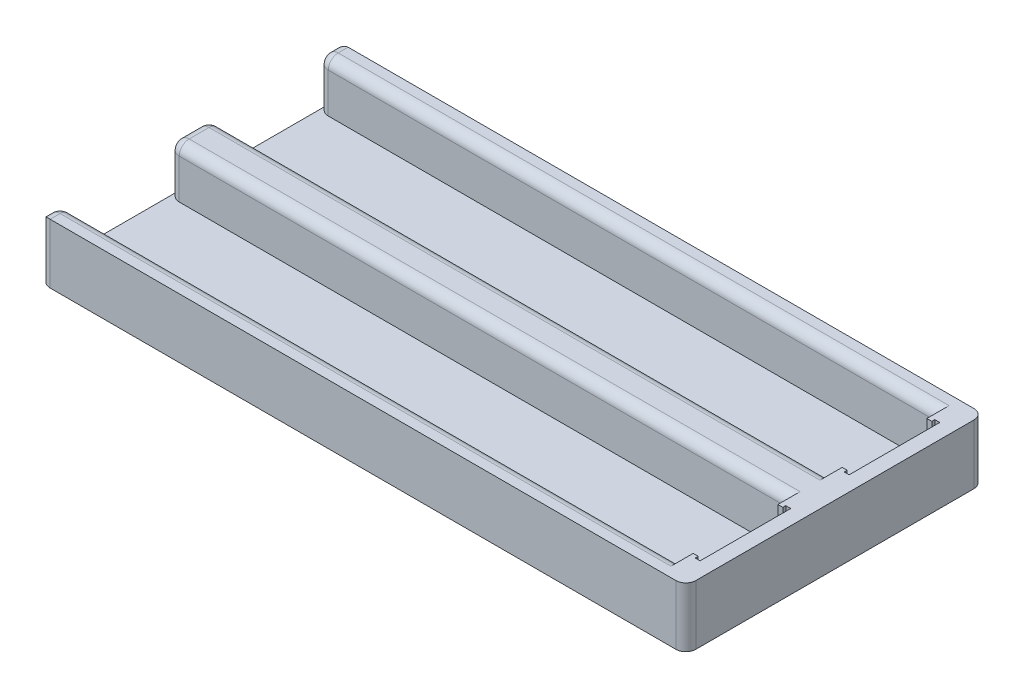
SolidWorks part; units mm, degrees
ref_plane "Front Plane" through (0, 0, 0) normal (0, 0, 1) x (1, 0, 0)
ref_plane "Top Plane" through (0, 0, 0) normal (0, 1, 0) x (1, 0, 0)
ref_plane "Right Plane" through (0, 0, 0) normal (1, 0, 0) x (0, 0, -1)
sketch "Sketch1" plane through (0, 0, 0) normal (0, 1, 0) x (1, 0, 0)
  line L1 (-65, 30) -> (65, 30)
  line L2 (-65, 30) -> (-65, -30)
  line L3 (-65, -30) -> (65, -30)
  line L4 (65, 30) -> (65, -30)
  line L5 (-65, 30) -> (65, -30) construction
  line L6 (-65, -30) -> (65, 30) construction
  point P0 (0, 0)
  dimension "D1" = 130
  dimension "D2" = 60
extrude "Boss-Extrude1" add sketch "Sketch1" along normal blind 12
ref_plane "Plane2" through (60, 0, 0) normal (1, 0, 0) x (0, 0, -1)
sketch "Sketch2" plane through (65, 0, 0) normal (1, 0, 0) x (0, 0, -1)
  line L0 (0, 0) -> (0, 12) construction
  line L1 (30, 0) -> (-30, 0)
  line L2 (30, 0) -> (30, 12)
  line L3 (30, 12) -> (-30, 12)
  line L4 (-30, 0) -> (-30, 12)
  line L5 (30, 0) -> (-30, 12) construction
  line L6 (30, 12) -> (-30, 0) construction
  line L8 (4, 12) -> (26, 12)
  line L9 (4, 12) -> (4, 2)
  line L10 (4, 2) -> (26, 2)
  line L11 (26, 12) -> (26, 2)
  line L12 (4, 12) -> (26, 2) construction
  line L13 (4, 2) -> (26, 12) construction
  point P4 (0, 6)
  point P14 (15, 7)
  dimension "D1" = 4
  dimension "D2" = 4
  dimension "D3" = 10
extrude "Cut-Extrude1" cut sketch "Sketch2" against normal through all from surface contours L11 L3 L9 L10 region at (65, 7, -15) starting at plane "Plane2"
ref_plane "Plane1" through (0, 0, 0) normal (0, 0, 1) x (1, 0, 0)
mirror "Mirror1" about plane through (0, 0, 0) normal (0, 0, 1) of "Cut-Extrude1"
sketch "Sketch3" plane through (60, 0, 0) normal (-1, 0, 0) x (0, 0, 1)
  line L0 (26, 12) -> (4, 12) construction
  line L1 (5.875, 12) -> (24.125, 12)
  line L2 (5.875, 12) -> (5.875, 3)
  line L3 (5.875, 3) -> (24.125, 3)
  line L4 (24.125, 12) -> (24.125, 3)
  line L5 (5.875, 12) -> (24.125, 3) construction
  line L6 (5.875, 3) -> (24.125, 12) construction
  line L7 (15, 7) -> (15, 12) construction
  line L8 (24.125, 12) -> (23.525, 12)
  line L9 (24.125, 12) -> (24.125, 3)
  line L10 (24.125, 3) -> (23.525, 3)
  line L11 (23.525, 12) -> (23.525, 3)
  line L12 (24.125, 12) -> (23.525, 3) construction
  line L13 (24.125, 3) -> (23.525, 12) construction
  line L14 (5.875, 12) -> (6.475, 12)
  line L15 (5.875, 12) -> (5.875, 3)
  line L16 (5.875, 3) -> (6.475, 3)
  line L17 (6.475, 12) -> (6.475, 3)
  line L18 (5.875, 12) -> (6.475, 3) construction
  line L19 (5.875, 3) -> (6.475, 12) construction
  line L20 (5.875, 3) -> (24.125, 3)
  line L21 (5.875, 3) -> (5.875, 3.6)
  line L22 (5.875, 3.6) -> (24.125, 3.6)
  line L23 (24.125, 3) -> (24.125, 3.6)
  line L24 (5.875, 3) -> (24.125, 3.6) construction
  line L25 (5.875, 3.6) -> (24.125, 3) construction
  line L26 (26, 2) -> (4, 2)
  line L27 (26, 2) -> (26, 12) construction
  line L28 (26, 12) -> (4, 12)
  line L29 (4, 2) -> (4, 12) construction
  line L30 (26, 2) -> (4, 12) construction
  line L31 (26, 12) -> (4, 2) construction
  point P4 (15, 7.5)
  point P9 (23.825, 7.5)
  point P12 (6.175, 7.5)
  point P15 (15, 3.3)
  point P20 (15, 7)
  line M12 (26, 12) -> (4, 12)
  dimension "D1" = 18.25
  dimension "D2" = 9
  dimension "D3" = 0.6
  dimension "D4" = 0.6
  dimension "D5" = 0.6
ref_plane "Plane3" through (62, 0, 0) normal (-1, 0, 0) x (0, 0, 1)
extrude "Cut-Extrude2" cut sketch "Sketch3" along normal blind 1 from surface contours L11 L22 L4 M12 | L22 L11 L3 L9 | L17 L22 L11 L1 | L22 L17 L3 L11 | L22 L15 L3 L17 | L2 L22 L17 M12 region at (60, 7.8, 6.175) region at (60, 7.8, 15) region at (60, 3.3, 6.175) region at (60, 7.8, 23.825) region at (60, 3.3, 15) region at (60, 3.3, 23.825) starting at plane "Plane3"
extrude "Cut-Extrude3" cut sketch "Sketch3<3>" along normal blind 2 from surface contours L17 L22 L11 L1 region at (60, 7.8, 15) starting at plane "Plane3"
sketch "Sketch3<3>" plane through (60, 0, 0) normal (-1, 0, 0) x (0, 0, 1) same geometry as "Sketch3"
mirror "Mirror2" about plane through (0, 0, 0) normal (0, 0, 1) of "Cut-Extrude3", "Cut-Extrude2"
fillet "Fillet1" radius 2 4 edges at (-2.5, 12, 26) (-2.5, 12, -26) (-2.5, 12, -4) (-2.5, 12, 4)
fillet "Fillet2" radius 2 15 edges at (-65, 12, -29) (-65, 11.4142, -26.5858) (-65, 6, -4) (-65, 11.4142, -3.4142) (-65, 12, 0) (-65, 11.4142, 3.4142) (-65, 12, 29) (-65, 11.4142, 26.5858) (65, 6, -30) (65, 6, 30) (-65, 6, 30) (-65, 6, -30) (-65, 6, -26) (-65, 6, 4) (-65, 6, 26)
